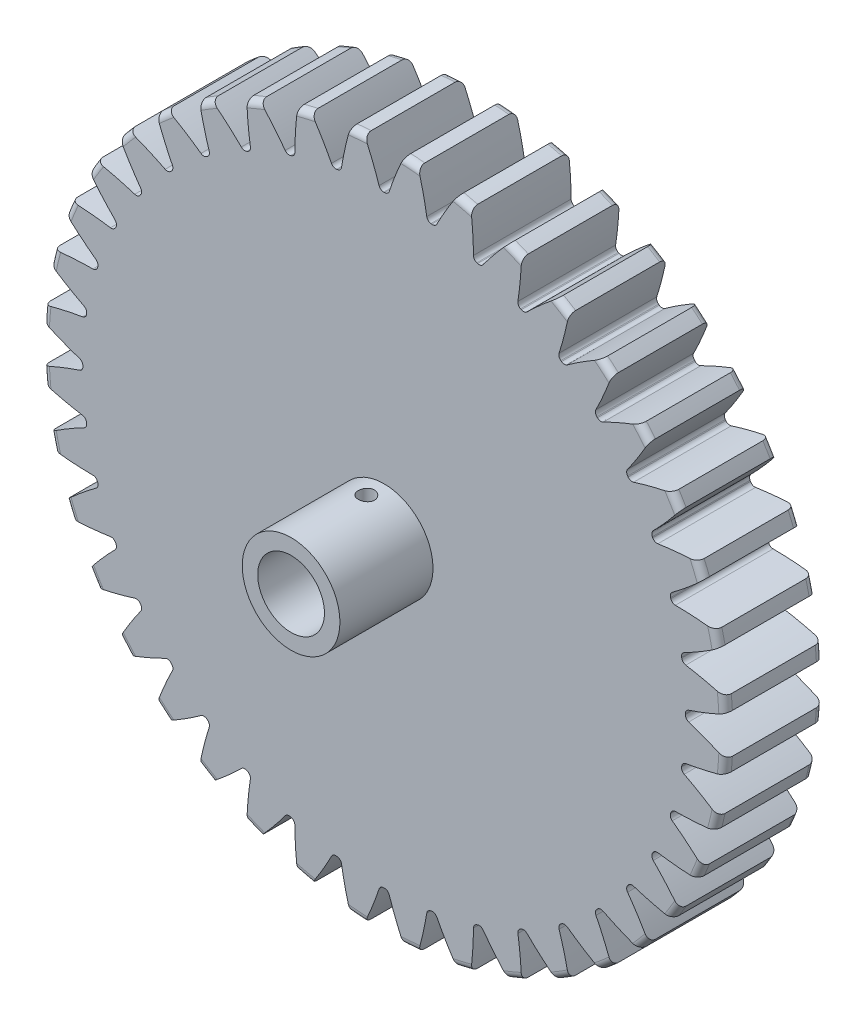
SolidWorks part; units mm, degrees
ref_plane "Front Plane" through (0, 0, 0) normal (0, 0, 1) x (1, 0, 0)
ref_plane "Top Plane" through (0, 0, 0) normal (0, 1, 0) x (1, 0, 0)
ref_plane "Right Plane" through (0, 0, 0) normal (1, 0, 0) x (0, 0, -1)
sketch "Sketch1" plane through (0, 0, 0) normal (0, 0, 1) x (1, 0, 0)
  line L0 (-508, 0) -> (508, 0) construction
  circle A0 centre (0, 0) radius 21 construction
  circle A1 centre (0, 0) radius 20 construction
  circle A2 centre (0, 0) radius 18.5 construction
  circle A3 centre (0, 0) radius 8 construction
  circle A4 centre (0, 0) radius 4 construction
  dimension "D2" = 1
  dimension "D3" = 2.5
  dimension "D1" = 2.5
sketch "Sketch2" plane through (0, 0, 0) normal (1, 0, 0) x (0, 0, -1)
  line L0 (0, 0) -> (-6, 0) construction
  line L1 (-6, 0) -> (-12, 0) construction
  dimension "Overall Width" = 12
  dimension "Face Width" = 6
sketch "Sketch4" plane through (0, 0, 0) normal (1, 0, 0) x (0, 0, -1)
  line L0 (-12, 4) -> (-12, 8)
  line L1 (-12, 8) -> (-6, 8)
  line L2 (-6, 8) -> (-6, 21)
  line L3 (-6, 21) -> (0, 21)
  line L4 (0, 21) -> (0, 4)
  line L5 (-6, 8) -> (-6, 0) construction
  line L6 (0, 21) -> (0, -21) construction
  line L7 (-6, 8) -> (0, 8) construction
  line L12 (-12, 4) -> (0, 4)
revolve "Revolve1" add sketch "Sketch4" angle 360 about L1
fillet "Fillet2" radius 0.42 4 edges at (0, 8, 12) (0, 8, 6) (0, 21, 6) (0, 21, 0)
sketch "Sketch7" plane through (0, 0, 6) normal (0, 0, 1) x (1, 0, 0)
  line L0 (0, 0) -> (0, 21) construction
  line L1 (0.7852, 19.9846) -> (1.1869, 20.9664) construction
  line L3 (1.6476, 20.9353) -> (1.5692, 19.9383) construction
  line L4 (1.5692, 19.9383) -> (1.4515, 18.443) construction
  line L5 (0, 0) -> (1.4515, 18.443) construction
  line L6 (0.7852, 19.9846) -> (0, 0) construction
  line L7 (0.7852, 19.9846) -> (0.8245, 20.9838) construction
  line L8 (0.7852, 19.9846) -> (0, 0) construction
  circle A0 centre (0, 0) radius 21 construction
  arc A1 (-0.027, 18.5) -> (0.027, 18.5) centre (0, 0) cw
  circle A2 centre (0, 0) radius 18.5 construction
  arc A3 (-0.7852, 19.9846) -> (0.7852, 19.9846) centre (0, 0) cw construction
  circle A4 centre (0, 0) radius 20 construction
  arc A5 (2.0774, 20.897) -> (1.2172, 20.9647) centre (0, 0) ccw construction
  arc A6 (0.7852, 19.9846) -> (2.3507, 19.8614) centre (0, 0) cw construction
  arc A7 (-1.2172, 20.9647) -> (1.2172, 20.9647) centre (0, 0) cw
  arc A8 (0.3122, 18.7056) -> (1.2172, 20.9647) centre (19.296, 12.4116) cw
  arc A9 (-0.3122, 18.7056) -> (-1.2172, 20.9647) centre (-19.296, 12.4116) ccw
  arc A10 (-0.027, 18.5) -> (-0.3122, 18.7056) centre (-0.0274, 18.8) cw
  arc A11 (0.027, 18.5) -> (0.3122, 18.7056) centre (0.0274, 18.8) ccw
  point P26 (-0.2447, 18.4984)
  point P29 (0.2447, 18.4984)
  dimension "D4" = 0.3
  dimension "D5" = 20
  dimension "D3" = 20
  dimension "D1" = 3.1416
  dimension "D2" = 1.5708
extrude "Cut-Extrude2" cut sketch "Sketch7" against normal through all
pattern_circular "CirPattern1" count 40 over 360 about axis through (0, 0, 12) along (0, 0, -1) of "Cut-Extrude2"
sketch "Sketch9" plane through (0, 0, 6) normal (0, 0, 1) x (1, 0, 0)
  circle A0 centre (0, 0) radius 8.42
  circle A1 centre (0, 0) radius 2.05
  circle A2 centre (0, 0) radius 3
  dimension "D1" = 16.84
  dimension "D2" = 4.1
  dimension "D3" = 6
extrude "Cut-Extrude3" cut sketch "Sketch9" along normal up to next contours A0 A2 region at (-8.1818, 0, 6)
extrude "Boss-Extrude1" add sketch "Sketch9<2>" against normal up to surface (6 mm away) contours A0 A2 | A2 A1 region at (-8.1818, 0, 6) region at (-2.9151, 0, 6) up to face at (0, 0, 0)
sketch "Sketch9<2>" plane through (0, 0, 6) normal (0, 0, 1) x (1, 0, 0) same geometry as "Sketch9"
extrude "Boss-Extrude2" add sketch "Sketch9<4>" along normal blind 5.715 and the other way blind 11.43 contours A2 A1 region at (-2.9151, 0, 6)
sketch "Sketch9<4>" plane through (0, 0, 6) normal (0, 0, 1) x (1, 0, 0) same geometry as "Sketch9"
ref_plane "Plane1" through (0, 3, 0) normal (0, 1, 0) x (1, 0, 0)
sketch "Sketch11" plane through (0, 3, 0) normal (0, 1, 0) x (1, 0, 0)
  line L0 (0.027, 0) -> (0.027, -6) construction
  line L1 (0.027, 1.124) -> (0.027, -7.124) construction
  circle A0 centre (0.027, 1.124) radius 0.5
  circle A1 centre (0.027, -7.124) radius 0.5
  point P4 (0.027, -3)
  point P5 (0.027, -3)
  dimension "D2" = 1
  dimension "D1" = 8.248
extrude "Cut-Extrude4" cut sketch "Sketch11" against normal through all contours A1 | A0 region at (0.027, 3, 7.124)
equation "\"D1@Sketch1\"=2.5*(\"Pitch Dia.@Sketch1\"/\"Number of Teeth@Sketch1\")"
equation "\"D1@CirPattern1\"=\"Number of Teeth@Sketch1\""
equation "\"D1@Fillet2\"=\"OD@Sketch1\"*.01"
equation "\"D1@Sketch7\"=3.14159*(\"Pitch Dia.@Sketch1\"/\"Number of Teeth@Sketch1\")"
equation "\"D2@Sketch7\"=\"D1@Sketch7\"/2"
equation "\"D4@Sketch7\"=\"D1@Sketch7\"*.0955"
equation "\"D5@Sketch7\"=\"Pitch Dia.@Sketch1\"/2"
